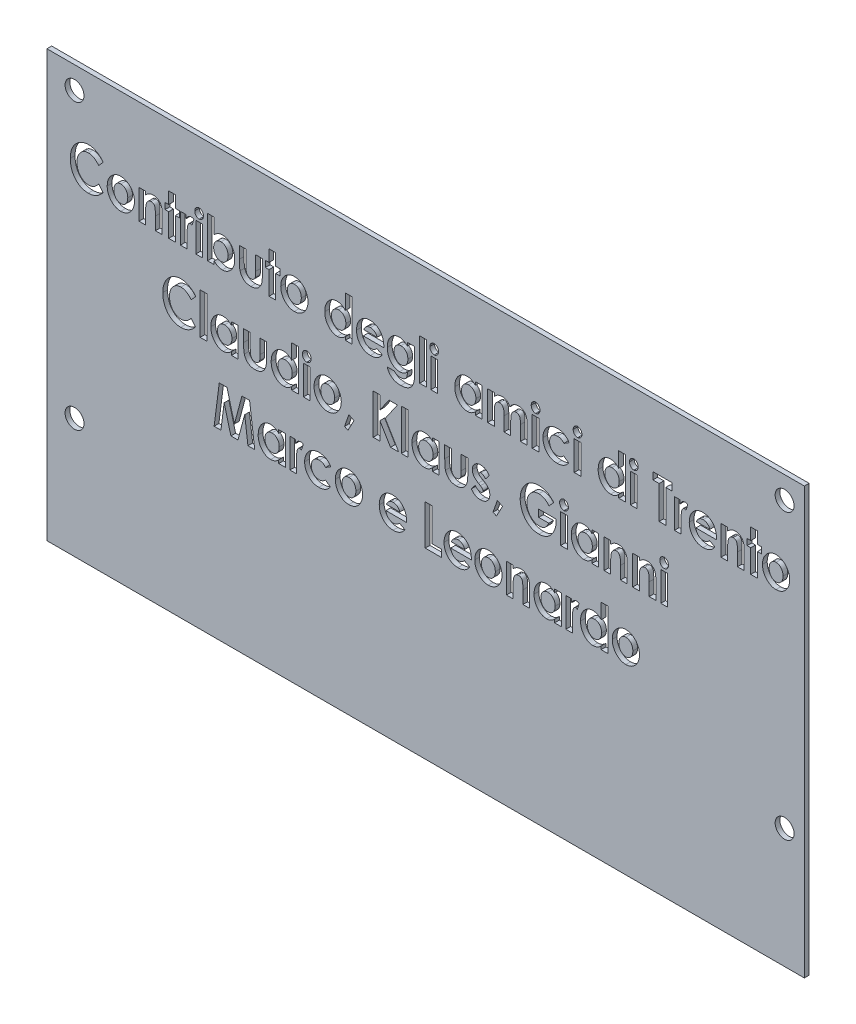
SolidWorks part; units mm, degrees
ref_plane "Piano frontale" through (0, 0, 0) normal (0, 0, 1) x (1, 0, 0)
ref_plane "Piano superiore" through (0, 0, 0) normal (0, 1, 0) x (1, 0, 0)
ref_plane "Piano destro" through (0, 0, 0) normal (1, 0, 0) x (0, 0, -1)
sketch "Schizzo1" plane through (0, 0, 0) normal (0, 0, 1) x (1, 0, 0)
  line L1 (0, 0) -> (160, 0)
  line L2 (0, 0) -> (0, 90)
  line L3 (0, 90) -> (160, 90)
  line L4 (160, 0) -> (160, 90)
  dimension "D1" = 90
  dimension "D2" = 160
extrude "Estrusione-Estrusione1" add sketch "Schizzo1" along normal blind 1
sketch "Schizzo3" plane through (0, 0, 1) normal (0, 0, 1) x (1, 0, 0)
  line L1 (5.8322, 85.3005) -> (155.8322, 85.3005)
  line L2 (5.8322, 85.3005) -> (5.8322, 25.3005)
  line L3 (5.8322, 25.3005) -> (155.8322, 25.3005)
  line L4 (155.8322, 85.3005) -> (155.8322, 25.3005)
  circle A0 centre (5.8322, 85.3005) radius 2
  circle A1 centre (155.8322, 85.3005) radius 2
  circle A2 centre (155.8322, 25.3005) radius 2
  circle A3 centre (5.8322, 25.3005) radius 2
  dimension "D1" = 4
  dimension "D2" = 150
  dimension "D3" = 60
extrude "Taglio-Estrusione1" cut sketch "Schizzo3" against normal blind 10 contours L1 A0 L2 | L2 A0 L1 | L4 A1 L1 | L1 A1 L4 | L3 A2 L4 | L4 A2 L3 | L3 A3 L2 | L2 A3 L3 region at (5.5492, 85.5834, 1) region at (6.681, 84.4517, 1) region at (156.1151, 85.5834, 1) region at (154.9833, 84.4517, 1) region at (6.681, 26.1493, 1) region at (5.5492, 25.0175, 1) region at (156.1151, 25.0175, 1) region at (154.9833, 26.1493, 1)
sketch "Schizzo4" plane through (0, 0, 1) normal (0, 0, 1) x (1, 0, 0)
  text T0 "<b>Contributo degli amici di Trento</b>\r\n<b>       Claudio, Klaus, Gianni</b>\r\n<b>           Marco e Leonardo</b>" font "Century Gothic" height in points 32
extrude "Taglio-Estrusione2" cut sketch "Schizzo4" against normal through all
